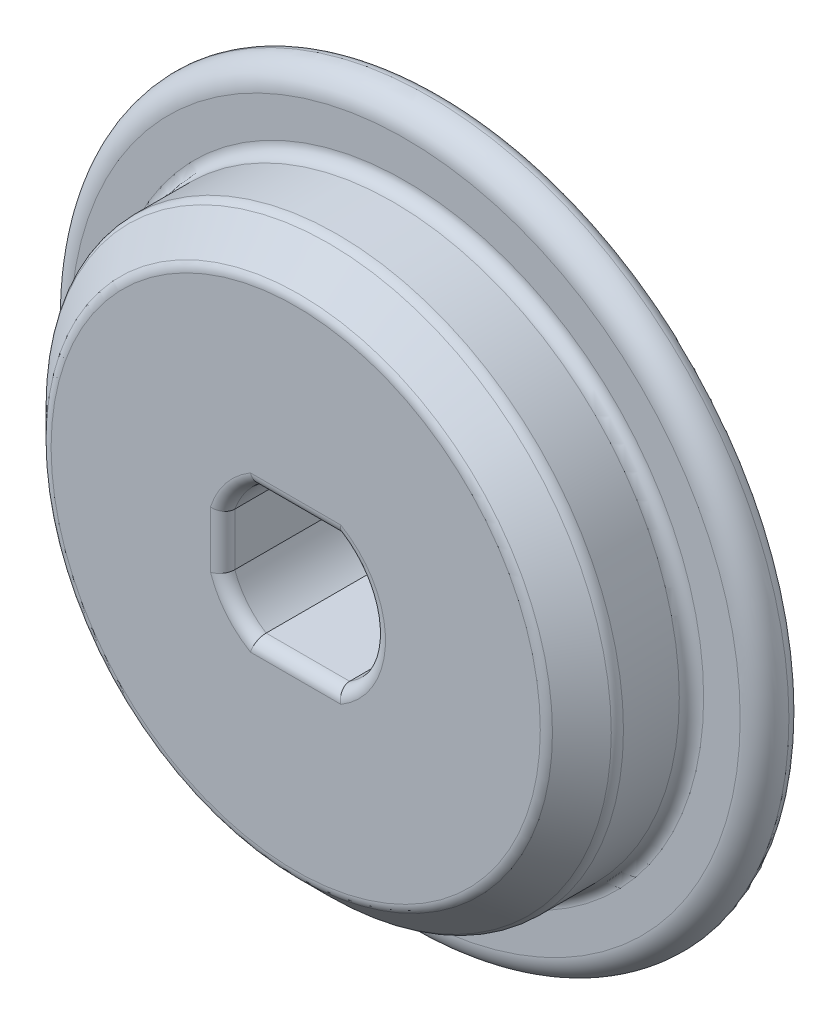
SolidWorks part; units mm, degrees
ref_plane "Front Plane" through (0, 0, 0) normal (0, 0, 1) x (1, 0, 0)
ref_plane "Top Plane" through (0, 0, 0) normal (0, 1, 0) x (1, 0, 0)
ref_plane "Right Plane" through (0, 0, 0) normal (1, 0, 0) x (0, 0, -1)
sketch "Sketch1" plane through (0, 0, 0) normal (0, 0, 1) x (1, 0, 0)
  circle A0 centre (0, 0) radius 29.5
  dimension "D1" = 59
extrude "Boss-Extrude1" add sketch "Sketch1" along normal blind 3
sketch "Sketch2" plane through (0, 0, 3) normal (0, 0, 1) x (1, 0, 0)
  circle A0 centre (0, 0) radius 23.5
  dimension "D1" = 47
extrude "Boss-Extrude2" add sketch "Sketch2" along normal blind 9
sketch "Sketch3" plane through (0, 0, 12) normal (0, 0, 1) x (1, 0, 0)
  line L0 (3.4278, 5.375) -> (-3.4278, 5.375)
  line L1 (3.4278, -5.375) -> (-3.4278, -5.375)
  line L2 (-6, 2.1542) -> (-6, -2.1542)
  circle A0 centre (0, 0) radius 6.375
  dimension "D1" = 12.75
  dimension "D2" = 10.75
  dimension "D3" = 6
extrude "Cut-Extrude1" cut sketch "Sketch3" against normal through all contours L0 A0 L1 region at (0.0568, 0, 12)
fillet "Fillet1" radius 2 1 edges at (29.5, 0, 3)
chamfer "Chamfer1" distance 3 angle 45 1 edges at (23.5, 0, 12)
fillet "Fillet2" radius 1 15 edges at (29.5, 0, 0) (20.5, 0, 12) (23.5, 0, 9) (6.375, 0, 12) (0, -5.375, 12) (-4.9814, 3.9782, 12) (0, 5.375, 12) (-6, 0, 12) (-4.9814, -3.9782, 12) (0, -5.375, 0) (-4.9814, -3.9782, 0) (-6, 0, 0) (-4.9814, 3.9782, 0) (0, 5.375, 0) (6.375, 0, 0)
fillet "Fillet3" radius 1 1 edges at (23.5, 0, 3)
sketch "Sketch4" plane through (0, 0, 12) normal (0, 0, 1) x (1, 0, 0)
  circle A0 centre (0, 0) radius 10.1801
